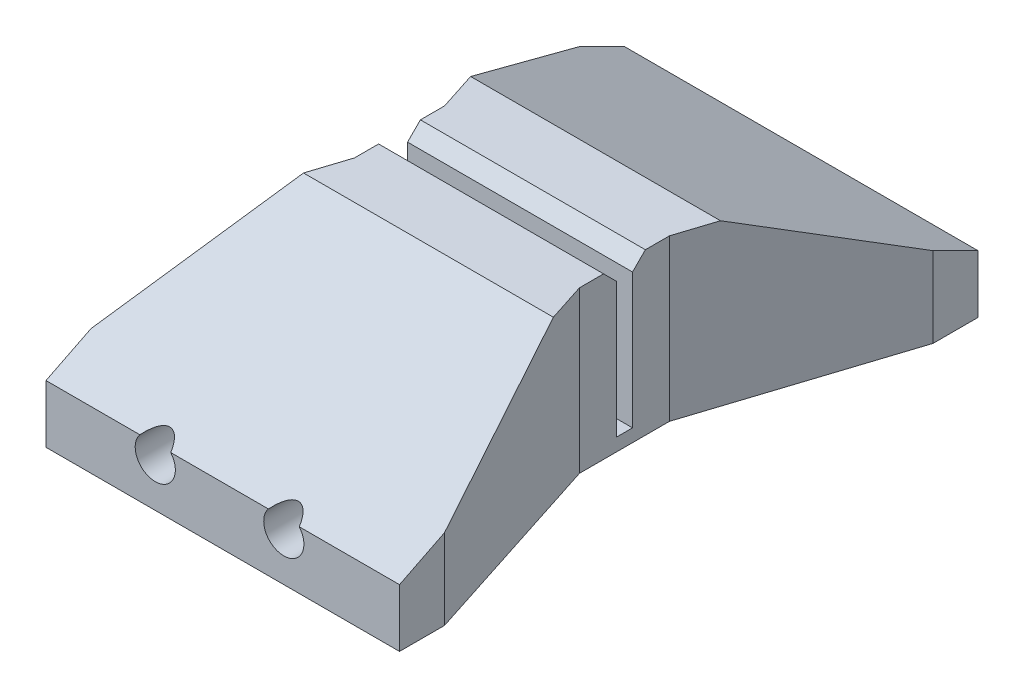
SolidWorks part; units mm, degrees
ref_plane "Front Plane" through (0, 0, 0) normal (0, 0, 1) x (1, 0, 0)
ref_plane "Top Plane" through (0, 0, 0) normal (0, 1, 0) x (1, 0, 0)
ref_plane "Right Plane" through (0, 0, 0) normal (1, 0, 0) x (0, 0, -1)
sketch "Sketch2" plane through (0, 0, 0) normal (0, 1, 0) x (1, 0, 0)
  line L1 (-34.925, -57.15) -> (34.925, -57.15)
  line L2 (-34.925, -57.15) -> (-34.925, 57.15)
  line L3 (-34.925, 57.15) -> (34.925, 57.15)
  line L4 (34.925, -57.15) -> (34.925, 57.15)
  line L5 (-34.925, -57.15) -> (34.925, 57.15) construction
  line L6 (-34.925, 57.15) -> (34.925, -57.15) construction
  point P0 (0, 0)
  dimension "D1" = 69.85
  dimension "D2" = 114.3
extrude "Boss-Extrude1" add sketch "Sketch2" along normal blind 31.75
sketch "Sketch3" plane through (-34.925, 0, 0) normal (-1, 0, 0) x (0, 0, 1)
  line L0 (-57.15, 11.43) -> (-16.51, 31.75)
  line L1 (16.51, 31.75) -> (57.15, 11.43)
  line L2 (-57.15, 31.75) -> (57.15, 31.75) construction
  line L4 (-57.15, 0) -> (57.15, 0)
  line L5 (57.15, 0) -> (57.15, 31.75)
  line L6 (57.15, 31.75) -> (-57.15, 31.75)
  line L7 (-57.15, 31.75) -> (-57.15, 0)
  line L8 (-57.15, 0) -> (57.15, 0)
  line L9 (57.15, 0) -> (57.15, 31.75)
  line L10 (57.15, 31.75) -> (-57.15, 31.75)
  line L11 (-57.15, 31.75) -> (-57.15, 0)
  point P8 (0, 31.75)
  point P9 (16.51, 25.4)
  line M8 (57.15, 0) -> (57.15, 31.75)
  line M9 (57.15, 31.75) -> (-57.15, 31.75)
  line M10 (-57.15, 31.75) -> (-57.15, 0)
  dimension "D2" = 16.51
  dimension "D3" = 11.43
  dimension "D4" = 11.43
  dimension "D1" = 0
extrude "Cut-Extrude1" cut sketch "Sketch3" against normal through all and the other way through all contours L1 M9 M8 | L0 M10 M9 region at (-34.925, 24.9767, -43.6033) region at (-34.925, 24.9767, 43.6033)
sketch "Sketch4" plane through (0, 31.75, 0) normal (0, 1, 0) x (1, 0, 0)
  line L0 (34.925, 0) -> (-34.925, 0) construction
  line L1 (34.925, -16.51) -> (34.925, 16.51) construction
  line L2 (-34.925, 16.51) -> (-34.925, -16.51) construction
  line L3 (34.925, 1.5875) -> (-34.925, 1.5875)
  line L4 (34.925, -1.5875) -> (-34.925, -1.5875)
  line M3 (34.925, -16.51) -> (34.925, 16.51)
  line M5 (-34.925, 16.51) -> (-34.925, -16.51)
  dimension "D1" = 1.5875
  dimension "D2" = 1.5875
extrude "Cut-Extrude2" cut sketch "Sketch4" against normal blind 29.21 contours L0 L3 M3 M5 | L0 L4 M3 M5 region at (0, 31.75, 0.7938) region at (0, 31.75, -0.7937)
chamfer "Chamfer1" distance 2.54 angle 45 2 edges at (0, 31.75, -1.5875) (0, 31.75, 1.5875)
sketch "Sketch5" plane through (0, 0, 0) normal (0, -1, 0) x (1, 0, 0)
  line L0 (-34.925, 25.4) -> (34.925, 25.4) construction
  line L1 (-34.925, 0) -> (34.925, 0) construction
  line L2 (-34.925, 48.26) -> (-22.225, 8.89)
  line L3 (-22.225, 8.89) -> (-22.225, -8.89)
  line L4 (34.925, -57.15) -> (34.925, 57.15)
  line L5 (34.925, 57.15) -> (-34.925, 57.15)
  line L6 (-34.925, 57.15) -> (-34.925, -57.15)
  line L7 (-34.925, -57.15) -> (34.925, -57.15)
  line L8 (34.925, -57.15) -> (34.925, 57.15)
  line L9 (34.925, 57.15) -> (-34.925, 57.15)
  line L10 (-34.925, 57.15) -> (-34.925, -57.15)
  line L11 (-34.925, -57.15) -> (34.925, -57.15)
  line L12 (0, 57.15) -> (0, 0) construction
  line L13 (22.225, 8.89) -> (22.225, -8.89)
  line L14 (34.925, 48.26) -> (22.225, 8.89)
  line L15 (34.925, -48.26) -> (22.225, -8.89)
  line L16 (-34.925, -48.26) -> (-22.225, -8.89)
  circle A0 centre (-21.59, 25.4) radius 2.032
  circle A1 centre (21.59, 25.4) radius 2.032
  circle A2 centre (21.59, -25.4) radius 2.032
  circle A3 centre (-21.59, -25.4) radius 2.032
  circle A4 centre (-8.89, 25.4) radius 2.032
  circle A5 centre (8.89, 25.4) radius 2.032
  circle A6 centre (-8.89, -25.4) radius 2.032
  circle A7 centre (8.89, -25.4) radius 2.032
  point P25 (22.225, 0)
  point P26 (-22.225, 0)
  point P37 (0, 0)
  line M15 (-34.925, 57.15) -> (-34.925, -57.15)
  dimension "D6" = 4.064
  dimension "D2" = 31.75
  dimension "D3" = 8.89
  dimension "D4" = 8.89
  dimension "D5" = 12.7
  dimension "D7" = 13.335
  dimension "D8" = 12.7
  dimension "D1" = 0
extrude "Cut-Extrude3" cut sketch "Sketch5" against normal through all and the other way through all contours L16 L3 L2 M15 | L15 L8 L14 L13 region at (-30.0331, 0, 0) region at (30.0331, 0, 0)
extrude "Cut-Extrude4" cut sketch "Sketch5<3>" against normal blind 9.525 contours A0 | A1 | A3 | A2 | A4 | A5 | A7 | A6
sketch "Sketch5<3>" plane through (0, 0, 0) normal (0, -1, 0) x (1, 0, 0) same geometry as "Sketch5"
sketch "Sketch6" plane through (0, 0, -1.5875) normal (0, 0, 1) x (1, 0, 0)
  line L4 (-22.225, 8.89) -> (22.225, 8.89) construction
  line L8 (-22.225, 29.21) -> (-22.225, 2.54)
  line L9 (-22.225, 2.54) -> (22.225, 2.54)
  line L10 (22.225, 2.54) -> (22.225, 29.21)
  line L11 (22.225, 29.21) -> (-22.225, 29.21)
  line L12 (-22.225, 29.21) -> (-22.225, 2.54)
  line L13 (-22.225, 2.54) -> (22.225, 2.54)
  line L14 (22.225, 2.54) -> (22.225, 29.21)
  line L15 (22.225, 29.21) -> (-22.225, 29.21)
  circle A0 centre (-13.335, 8.89) radius 2.032
  circle A1 centre (12.065, 8.89) radius 2.032
  circle A2 centre (-13.335, 8.89) radius 3.9688
  circle A3 centre (12.065, 8.89) radius 3.9688
  point P13 (-12.703, 15.24)
  dimension "D4" = 4.064
  dimension "D6" = 7.9375
  dimension "D2" = 6.35
  dimension "D3" = 25.4
  dimension "D5" = 8.89
  dimension "D1" = 0
extrude "Cut-Extrude6" cut sketch "Sketch6" against normal blind 12.7 and the other way through all contours A0 | A1
ref_plane "Plane1" through (0, 0, 4.7625) normal (0, 0, -1) x (-1, 0, 0)
sketch "Sketch7" plane through (0, 0, 4.7625) normal (0, 0, -1) x (-1, 0, 0)
  circle A0 centre (-12.065, 8.89) radius 3.9688 construction
  circle A1 centre (13.335, 8.89) radius 3.9688 construction
  circle A3 centre (13.335, 8.89) radius 3.9688
  circle A4 centre (-12.065, 8.89) radius 3.9688
extrude "Cut-Extrude7" cut sketch "Sketch7" against normal up to next contours A4 | A3
